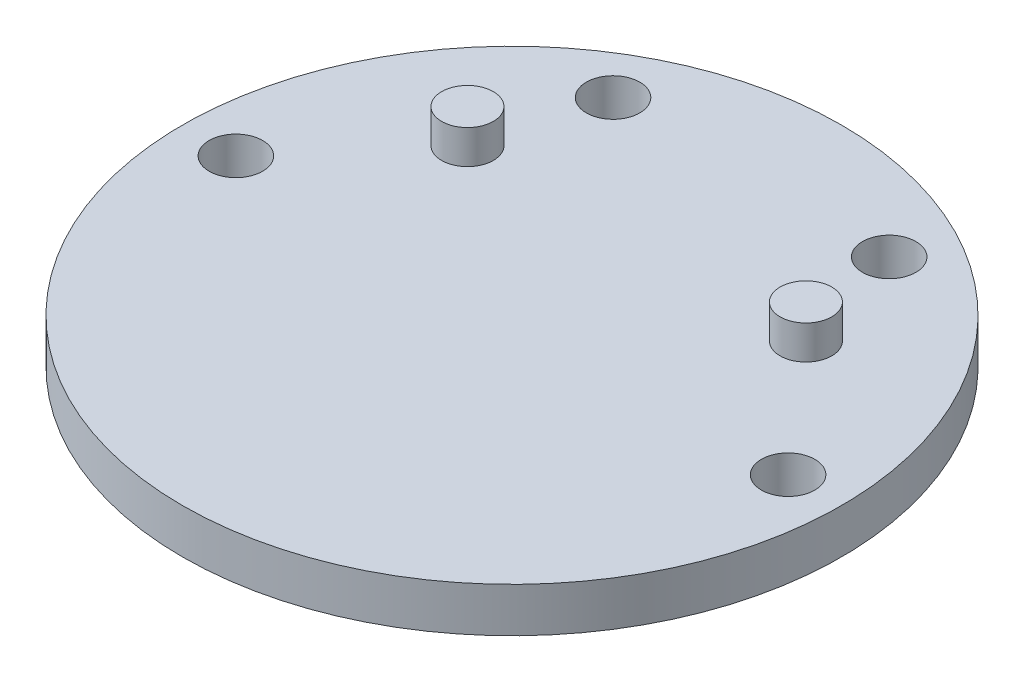
SolidWorks part; units mm, degrees
ref_plane "Front Plane" through (0, 0, 0) normal (0, 0, 1) x (1, 0, 0)
ref_plane "Top Plane" through (0, 0, 0) normal (0, 1, 0) x (1, 0, 0)
ref_plane "Right Plane" through (0, 0, 0) normal (1, 0, 0) x (0, 0, -1)
sketch "Sketch1" plane through (0, 0, 0) normal (0, 1, 0) x (1, 0, 0)
  line L4 (0, 0) -> (15.8817, 0) construction
  line L5 (0, 0) -> (0, 17.0912) construction
  line L6 (-7.75, 13.4234) -> (0, 0) construction
  line L7 (0, 0) -> (7.75, 13.4234) construction
  circle A0 centre (0, 0) radius 15.5 construction
  circle A1 centre (-7.75, 13.4234) radius 1.5
  circle A3 centre (-15.5, 0) radius 1.5
  circle A4 centre (7.75, 13.4234) radius 1.5
  circle A5 centre (15.5, 0) radius 1.5
  circle A6 centre (0, 0) radius 18.5
  dimension "D1" = 31
  dimension "D2" = 3
  dimension "D4" = 37
  dimension "D3" = 60
extrude "Boss-Extrude1" add sketch "Sketch1" along normal blind 2.5
sketch "Sketch2" plane through (0, 2.5, 0) normal (0, 1, 0) x (1, 0, 0)
  line L0 (0, 0) -> (0, 16.6144) construction
  line L1 (0, 0) -> (25.2906, 0) construction
  line L2 (-9.5, 7) -> (9.5, 7) construction
  circle A0 centre (-9.5, 7) radius 1.45
  circle A1 centre (9.5, 7) radius 1.45
  point P8 (0, 8.3072)
  point P11 (0, 7)
  dimension "D3" = 2.9
  dimension "D1" = 7
  dimension "D2" = 19
extrude "Boss-Extrude2" add sketch "Sketch2" along normal blind 1.9
